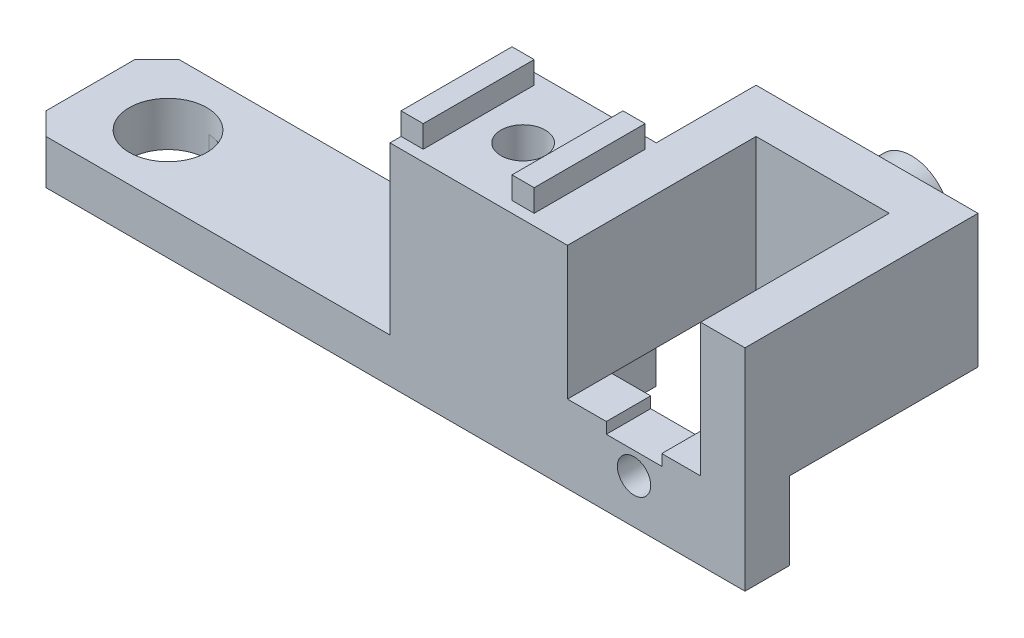
SolidWorks part; units mm, degrees
material "Plain Carbon Steel"
ref_plane "Front Plane" through (0, 0, 0) normal (0, 0, 1) x (1, 0, 0)
ref_plane "Top Plane" through (0, 0, 0) normal (0, 1, 0) x (1, 0, 0)
ref_plane "Right Plane" through (0, 0, 0) normal (1, 0, 0) x (0, 0, -1)
sketch "Sketch1" plane through (0, 0, 0) normal (0, 1, 0) x (1, 0, 0)
  line L0 (33, 6) -> (33, -6)
  line L1 (0, 6) -> (45, 6)
  line L2 (0, 6) -> (0, -6)
  line L3 (0, -6) -> (45, -6)
  line L4 (45, 6) -> (45, -6)
  line L5 (0, 0) -> (45, 0) construction
  line L14 (45, -2) -> (65, -2)
  line L15 (45, -2) -> (45, -6)
  line L16 (45, -6) -> (65, -6)
  line L17 (65, -2) -> (65, -6)
  line L18 (33, 5) -> (35, 5)
  line L19 (33, 5) -> (33, -5)
  line L20 (33, -5) -> (35, -5)
  line L21 (35, 5) -> (35, -5)
  line L22 (43, 5) -> (45, 5)
  line L23 (43, 5) -> (43, -5)
  line L24 (43, -5) -> (45, -5)
  line L25 (45, 5) -> (45, -5)
  circle A0 centre (7, 0) radius 3.5
  circle A2 centre (39.0887, 0) radius 2.1822
  dimension "D1" = 7
  dimension "D2" = 4
  dimension "D3" = 20
  dimension "D4" = 10
  dimension "D5" = 10
  dimension "D6" = 33
  dimension "D7" = 7
  dimension "D8" = 45
  dimension "D9" = 6
  dimension "D10" = 2
  dimension "D11" = 2
extrude "Boss-Extrude1" add sketch "Sketch1" along normal blind 4 contours L2 L5 A0 L0 L1 | L5 L2 L3 L0 L19 A0 region at (17.5226, 0, -3.163) region at (17.5226, 0, 3.163)
extrude "Boss-Extrude2" add sketch "Sketch1<3>" along normal blind 19 contours L5 L21 L20 L0 L3 L15 L24 L23 A2 | L21 L5 A2 L23 L22 L4 L1 L0 L18 | L0 L5 L21 L18 | L5 L19 L20 L21 | A2 L5 | L5 A2 | L23 L24 L25 L22 | L21 L20 L19 L18 region at (38.9851, 0, -3.5731) region at (34, 0, -2.5) region at (34, 0, 2.5) region at (38.9851, 0, 3.5731) region at (39.0887, 0, -0.9261) region at (39.0887, 0, 0.9261)
sketch "Sketch1<3>" plane through (0, 0, 0) normal (0, 1, 0) x (1, 0, 0) same geometry as "Sketch1"
extrude "Boss-Extrude3" add sketch "Sketch1<4>" along normal blind 7 contours L17 L14 L4 L15 L16 region at (55, 0, 4)
sketch "Sketch1<4>" plane through (0, 0, 0) normal (0, 1, 0) x (1, 0, 0) same geometry as "Sketch1"
extrude "Boss-Extrude4" add sketch "Sketch1<6>" along normal blind 2 from surface contours L5 L19 L20 L21 | L0 L5 L21 L18 | L5 L23 L24 L4 L25 | L23 L5 L4 L22 region at (34, 0, -2.5) region at (34, 0, 2.5) region at (44, 0, -2.5) region at (44, 0, 2.5) starting at face at (39, 19, 0)
sketch "Sketch1<6>" plane through (0, 0, 0) normal (0, 1, 0) x (1, 0, 0) same geometry as "Sketch1"
sketch "Sketch2" plane through (0, 7, 0) normal (0, 1, 0) x (1, 0, 0)
  line L0 (65, -2) -> (65, -6) construction
  line L2 (45, -6) -> (45, 15)
  line L3 (45, 15) -> (65, 15)
  line L4 (65, -6) -> (65, 15)
  line L6 (49, -6) -> (49, 11)
  line L7 (49, 11) -> (61, 11)
  line L8 (61, -6) -> (61, 11)
  line L9 (45, -6) -> (49, -6)
  line L10 (61, -6) -> (65, -6)
  line L11 (45, -6) -> (65, -6) construction
  dimension "D1" = 21
  dimension "D2" = 4
extrude "Boss-Extrude5" add sketch "Sketch2" along normal up to surface (12 mm away) up to face at (39, 19, 0)
sketch "Sketch4" plane through (0, 0, -15) normal (0, 0, -1) x (-1, 0, 0)
  line L0 (-65, 19) -> (-45, 7) construction
  circle A0 centre (-55, 13) radius 3.5
  dimension "D1" = 7
extrude "Boss-Extrude6" add sketch "Sketch4" along normal blind 4 contours A0 L0 | L0 A0 region at (54.2357, 14.2738, -15) region at (55.7643, 11.7262, -15)
sketch "Sketch5" plane through (0, 0, 6) normal (0, 0, 1) x (1, 0, 0)
  line L0 (49, 7) -> (61, 7) construction
  line L1 (52.5, 7) -> (57.5, 7)
  line L2 (52.5, 7) -> (52.5, 6)
  line L3 (52.5, 6) -> (57.5, 6)
  line L4 (57.5, 7) -> (57.5, 6)
  line L5 (0, 0) -> (65, 0) construction
  line L6 (55, 7) -> (55, 0) construction
  line L7 (49, 7) -> (61, 7) construction
  line L8 (55, 0) -> (55, 7) construction
  circle A0 centre (55, 4) radius 1.5
  dimension "D3" = 3
  dimension "D1" = 5
  dimension "D2" = 1
  dimension "D4" = 4
extrude "Cut-Extrude1" cut sketch "Sketch5" against normal through all
sketch "Sketch6" plane through (0, 19, 0) normal (0, 1, 0) x (1, 0, 0)
  line L0 (35, 5) -> (43, -5) construction
  circle A0 centre (39, 0) radius 2
  dimension "D1" = 4
extrude "Cut-Extrude2" cut sketch "Sketch6" against normal offset from surface 10 and the other way through all up to face at (7, 0, 3.5)
sketch "Sketch7" plane through (0, 10, 0) normal (0, 1, 0) x (1, 0, 0)
  circle A0 centre (39, 0) radius 3.5
  circle M2 centre (39, 0) radius 2
  dimension "D1" = 7
extrude "Cut-Extrude3" cut sketch "Sketch7" against normal through all contours A0 M2 | M2 | A0 region at (35.599, 10, 0) region at (39, 10, 0)
sketch "Sketch8" plane through (0, 0, 0) normal (0, -1, 0) x (1, 0, 0)
  line L0 (7.2188, 3.4932) -> (31.125, 1.9961)
  line L1 (7.2188, -3.4932) -> (31.125, -1.9961)
  arc A0 (31.125, -1.9961) -> (31.125, 1.9961) centre (31, 0) ccw
  circle A1 centre (7, 0) radius 3.5 construction
  circle A2 centre (7, 0) radius 3.5
  circle M5 centre (7, 0) radius 3.5
  dimension "D1" = 2
  dimension "D2" = 24
extrude "Cut-Extrude4" cut sketch "Sketch8" against normal blind 2 contours L1 A0 L0 M5 region at (20.1634, 0, 0)
chamfer "Chamfer1" distance 2 angle 45 2 edges at (0, 2, -6) (0, 2, 6)
